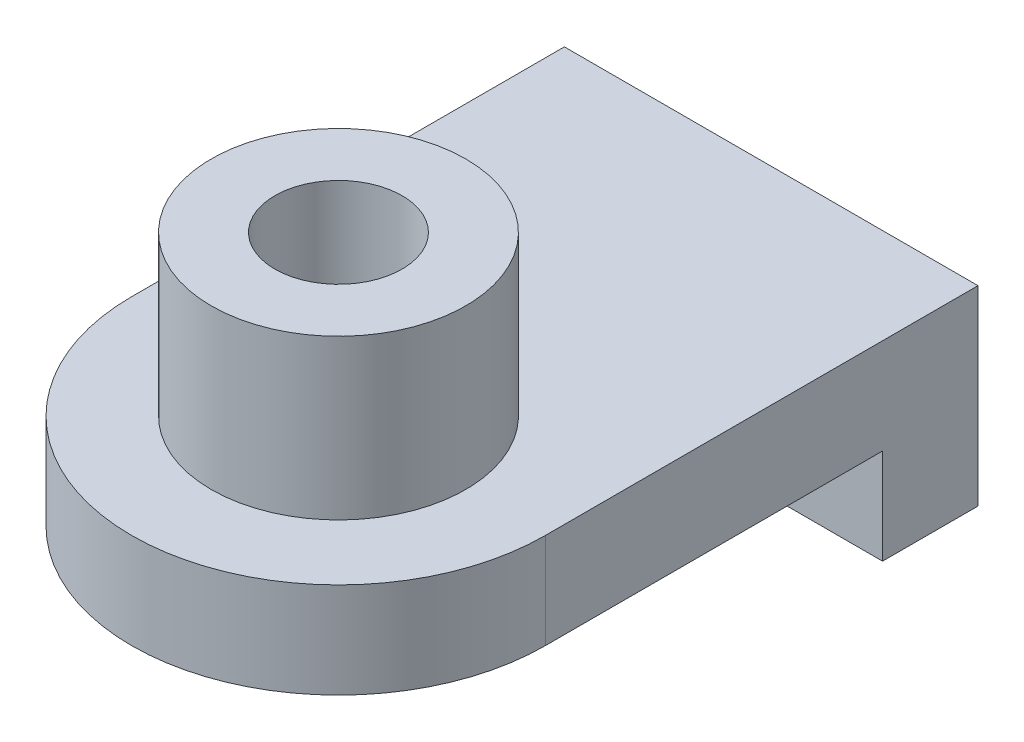
SolidWorks part; units mm, degrees
ref_plane "Alzado" through (0, 0, 0) normal (0, 0, 1) x (1, 0, 0)
ref_plane "Planta" through (0, 0, 0) normal (0, 1, 0) x (1, 0, 0)
ref_plane "Vista lateral" through (0, 0, 0) normal (1, 0, 0) x (0, 0, -1)
sketch "Sketch3" plane through (0, 0, 0) normal (0, 1, 0) x (1, 0, 0)
  line L0 (-32.5, 53) -> (32.5, 53)
  line L2 (-32.5, 0) -> (-32.5, 68)
  line L3 (-32.5, 68) -> (32.5, 68)
  line L4 (32.5, 0) -> (32.5, 68)
  circle A0 centre (0, 0) radius 10
  circle A1 centre (0, 0) radius 20
  arc A2 (-32.5, 0) -> (32.5, 0) centre (0, 0) ccw
  dimension "D1" = 20
  dimension "D2" = 40
  dimension "D3" = 65
  dimension "D4" = 68
  dimension "D5" = 15
extrude "Boss-Extrude4" add sketch "Sketch3" along normal blind 40 contours A1 A0 region at (-19.4343, 0, 0)
extrude "Boss-Extrude5" add sketch "Sketch3<7>" along normal blind 15 contours L2 A2 L4 L0 A1 region at (0, 0, -51.926)
sketch "Sketch3<7>" plane through (0, 0, 0) normal (0, 1, 0) x (1, 0, 0) same geometry as "Sketch3"
extrude "Boss-Extrude6" add sketch "Sketch3<8>" along normal blind 15 and the other way blind 15 contours L0 L4 L3 L2 region at (0, 0, -60.5)
sketch "Sketch3<8>" plane through (0, 0, 0) normal (0, 1, 0) x (1, 0, 0) same geometry as "Sketch3"
